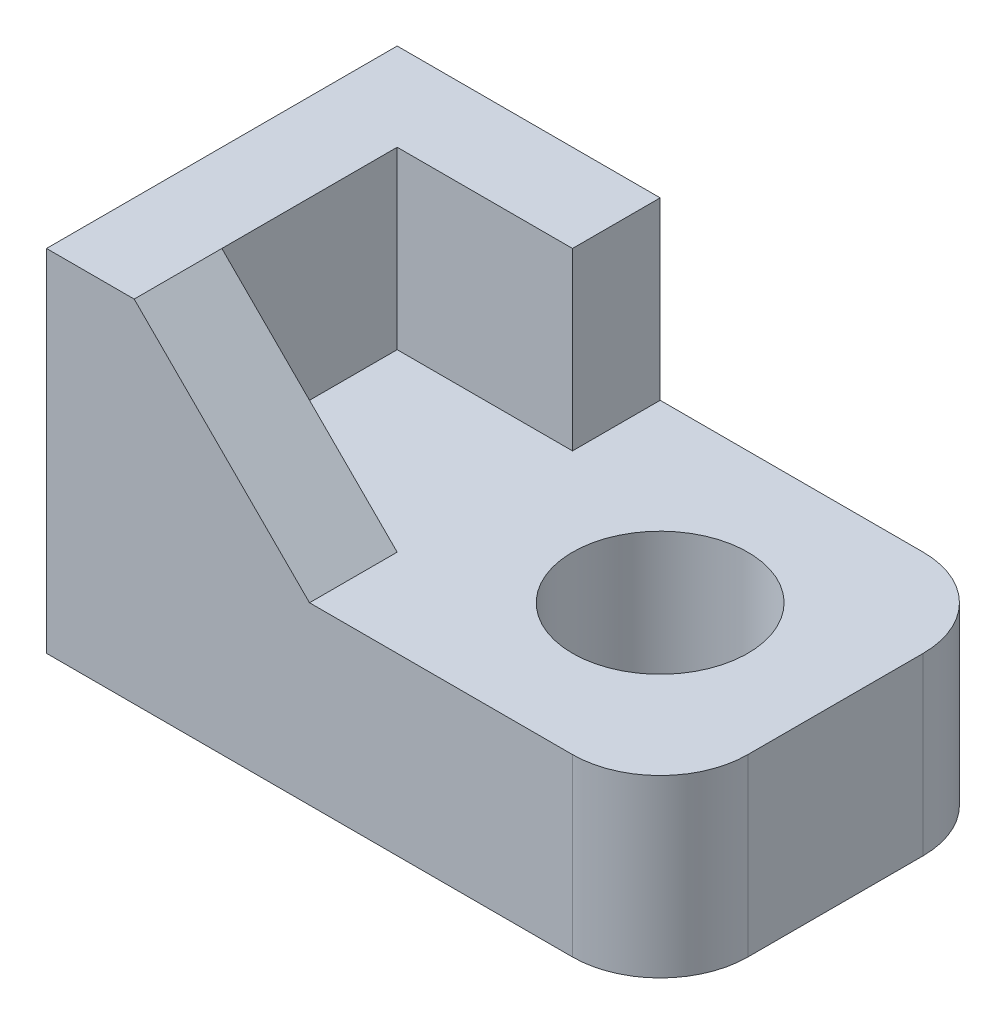
SolidWorks part; units mm, degrees
ref_plane "Front Plane" through (0, 0, 0) normal (0, 0, 1) x (1, 0, 0)
ref_plane "Top Plane" through (0, 0, 0) normal (0, 1, 0) x (1, 0, 0)
ref_plane "Right Plane" through (0, 0, 0) normal (1, 0, 0) x (0, 0, -1)
sketch "Sketch2" plane through (0, 0, 0) normal (0, 1, 0) x (1, 0, 0)
  line L1 (-10, 0) -> (-70, 0)
  line L2 (0, 10) -> (0, 30)
  line L3 (-10, 40) -> (-70, 40)
  line L4 (-70, 0) -> (-70, 40)
  arc A0 (0, 30) -> (-10, 40) centre (-10, 30) ccw
  arc A1 (-10, 0) -> (0, 10) centre (-10, 10) ccw
  point P9 (0, 0)
  dimension "D3" = 10
  dimension "D1" = 70
  dimension "D2" = 40
extrude "Boss-Extrude2" add sketch "Sketch2" against normal blind 20
sketch "Sketch3" plane through (0, 0, 0) normal (0, 1, 0) x (1, 0, 0)
  line L0 (-10, 40) -> (-70, 40) construction
  line L1 (-70, 40) -> (-70, 0) construction
  circle A0 centre (-20, 20) radius 10
  dimension "D1" = 20
  dimension "D2" = 20
  dimension "D3" = 50
extrude "Cut-Extrude1" cut sketch "Sketch3" against normal through all
sketch "Sketch5" plane through (0, 0, 0) normal (0, 1, 0) x (1, 0, 0)
  line L0 (-70, 40) -> (-40, 40)
  line L1 (-10, 40) -> (-70, 40) construction
  line L2 (-40, 40) -> (-40, 30)
  line L3 (-40, 30) -> (-60, 30)
  line L4 (-60, 30) -> (-60, 0)
  line L5 (-70, 0) -> (-10, 0) construction
  line L6 (-60, 0) -> (-70, 0)
  line L7 (-70, 0) -> (-70, 40)
  dimension "D1" = 10
  dimension "D2" = 20
extrude "Boss-Extrude3" add sketch "Sketch5" along normal blind 20
sketch "Sketch6" plane through (0, 0, 0) normal (0, 0, 1) x (1, 0, 0)
  line L0 (-60, 20) -> (-40, 0)
rib "Rib1" sketch "Sketch6" sketch "Sketch6" thickness 10 extrusion direction parallel to sketch draft on no parameters "D1"=10
